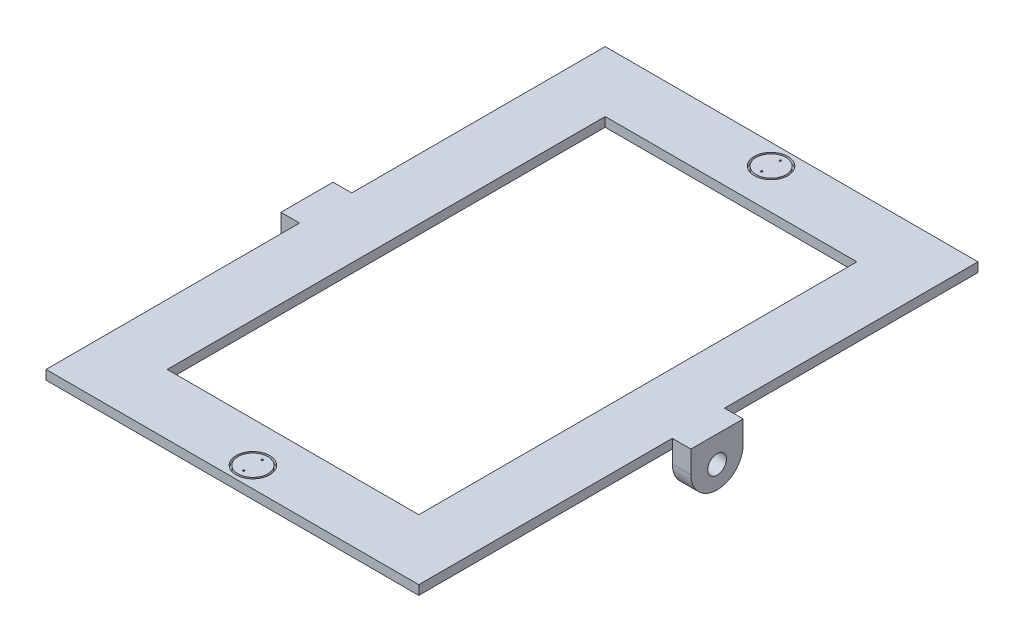
SolidWorks part; units mm, degrees
ref_plane "Front Plane" through (0, 0, 0) normal (0, 0, 1) x (1, 0, 0)
ref_plane "Top Plane" through (0, 0, 0) normal (0, 1, 0) x (1, 0, 0)
ref_plane "Right Plane" through (0, 0, 0) normal (1, 0, 0) x (0, 0, -1)
sketch "Sketch1" plane through (0, 0, 0) normal (0, 1, 0) x (1, 0, 0)
  line L1 (-100, 150) -> (100, 150)
  line L2 (-100, 150) -> (-100, -150)
  line L3 (-100, -150) -> (100, -150)
  line L4 (100, 150) -> (100, -150)
  line L5 (-100, 150) -> (100, -150) construction
  line L6 (-100, -150) -> (100, 150) construction
  line L7 (-67.5, 117.5) -> (67.5, 117.5)
  line L8 (-67.5, 117.5) -> (-67.5, -117.5)
  line L9 (-67.5, -117.5) -> (67.5, -117.5)
  line L10 (67.5, 117.5) -> (67.5, -117.5)
  line L11 (-67.5, 117.5) -> (67.5, -117.5) construction
  line L12 (-67.5, -117.5) -> (67.5, 117.5) construction
  point P0 (0, 0)
  point P6 (0, 0)
  dimension "D1" = 200
  dimension "D2" = 300
  dimension "D3" = 135
  dimension "D4" = 235
extrude "Boss-Extrude1" add sketch "Sketch1" along normal blind 5
sketch "Sketch3" plane through (100, 0, 0) normal (1, 0, 0) x (0, 0, -1)
  line L0 (-150, 5) -> (150, 5) construction
  line L1 (-14, 5) -> (14, 5)
  line L2 (-14, 5) -> (-14, -7)
  line L4 (14, 5) -> (14, -7)
  line L5 (0, 5) -> (0, -21) construction
  arc A0 (14, -7) -> (-14, -7) centre (0, -7) cw
  circle A1 centre (0, -9.1274) radius 5
  dimension "D3" = 14
  dimension "D4" = 10
  dimension "D1" = 28
  dimension "D2" = 12
extrude "Boss-Extrude2" add sketch "Sketch3" along normal blind 10
mirror "Mirror1" about plane through (0, 0, 0) normal (1, 0, 0) of "Boss-Extrude2"
sketch "Sketch4" plane through (0, 5, 0) normal (0, 1, 0) x (1, 0, 0)
  line L0 (0, 150) -> (0, -150) construction
  line L1 (100, 150) -> (-100, 150) construction
  line L2 (-100, -150) -> (100, -150) construction
  circle A0 centre (0, -139) radius 9
  circle A1 centre (0, -139) radius 8
  dimension "D1" = 18
  dimension "D2" = 16
  dimension "D3" = 11
extrude "Cut-Extrude1" cut sketch "Sketch4" against normal blind 2
mirror "Mirror2" about plane through (0, 0, 0) normal (0, 0, 1) of "Cut-Extrude1"
sketch "Sketch5" plane through (0, 5, 0) normal (0, 1, 0) x (1, 0, 0)
  line L0 (0, -130) -> (0, -148) construction
  line L1 (-9, -139) -> (9, -139) construction
  circle A0 centre (0, -139) radius 9 construction
  circle A1 centre (0, -139) radius 9 construction
  circle A2 centre (0, -134) radius 0.5
  circle A3 centre (0, -144) radius 0.5
  point P13 (0, -139)
  dimension "D1" = 1
  dimension "D2" = 1
  dimension "D3" = 10
  dimension "D4" = 5
extrude "Cut-Extrude2" cut sketch "Sketch5" against normal up to surface (5 mm away) up to face at (0, 0, 0)
mirror "Mirror3" about plane through (0, 0, 0) normal (0, 0, 1) of "Cut-Extrude2"
